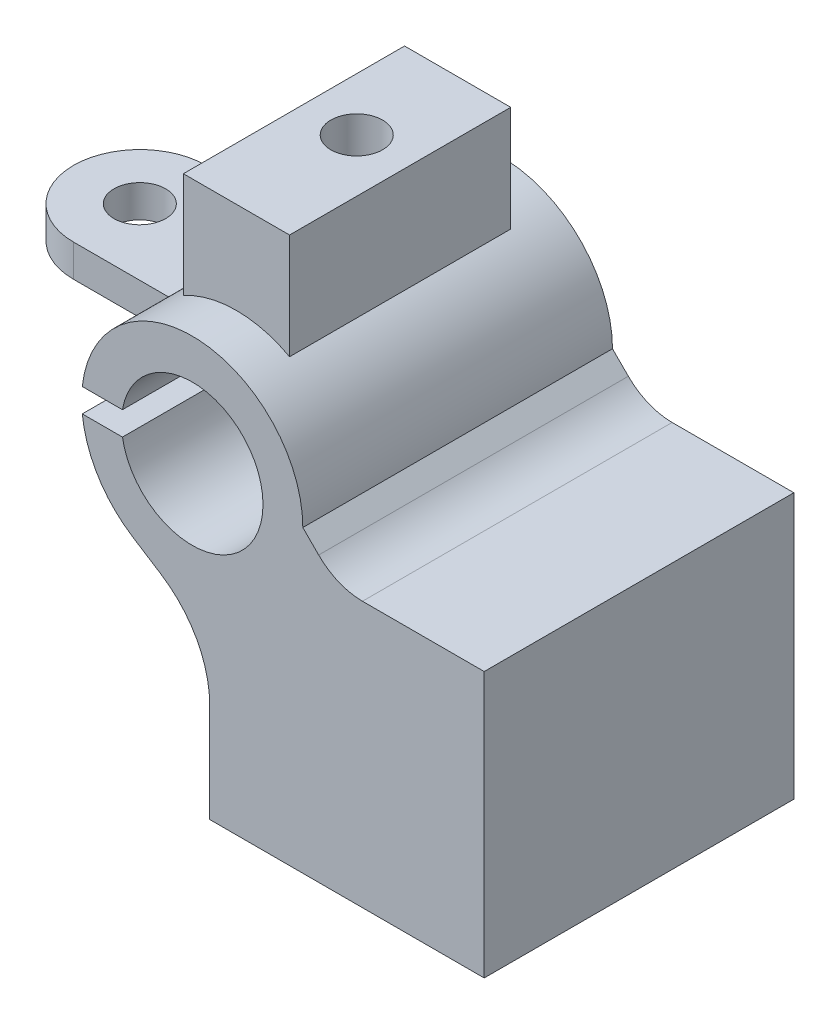
SolidWorks part; units mm, degrees
ref_plane "Front Plane" through (0, 0, 0) normal (0, 0, 1) x (1, 0, 0)
ref_plane "Top Plane" through (0, 0, 0) normal (0, 1, 0) x (1, 0, 0)
ref_plane "Right Plane" through (0, 0, 0) normal (1, 0, 0) x (0, 0, -1)
sketch "Sketch1" plane through (0, 0, 0) normal (0, 0, 1) x (1, 0, 0)
  line L0 (12.5, 0) -> (14.2931, -1.7931)
  line L1 (19.2428, -3.8433) -> (33, -3.8433)
  line L2 (33, -3.8433) -> (33, -33.8433)
  line L3 (33, -33.8433) -> (1.9777, -33.8433)
  line L4 (1.9777, -33.8433) -> (1.9777, -22.6745)
  line L6 (0, 0) -> (0, 50000) construction
  line L7 (-3.5519, -12.5684) -> (-6.74, -10.5272)
  line L8 (0, 0) -> (-50000, 0) construction
  line L9 (-7.8872, 1.3388) -> (-12.4281, 1.3388)
  line L10 (-7.8872, -1.3388) -> (-12.4281, -1.3388)
  line L11 (-6, 10.9659) -> (-6, 22.8852)
  line L12 (-6, 22.8852) -> (6, 22.8852)
  line L13 (6, 22.8852) -> (6, 10.9659)
  line L14 (-12.4281, 1.3388) -> (-30.9237, 1.3388)
  line L15 (-30.9237, 1.3388) -> (-30.9237, 4.9871)
  line L16 (-30.9237, 4.9871) -> (-11.4621, 4.9871)
  circle A0 centre (0, 0) radius 8
  arc A1 (12.5, 0) -> (-6.74, -10.5272) centre (0, 0) ccw
  arc A2 (14.2931, -1.7931) -> (19.2428, -3.8433) centre (19.2428, 3.1567) ccw
  arc A3 (1.9777, -22.6745) -> (-3.5519, -12.5684) centre (-10.0223, -22.6745) ccw
  point P24 (0, 0)
  point P30 (0, 0)
  point P31 (0, 0)
  point P32 (0, 0)
  point P33 (0, 0)
  dimension "D1" = 16
  dimension "D2" = 25
  dimension "D3" = 7
  dimension "D5" = 12
  dimension "D4" = 30
  dimension "D6" = 33
  dimension "D7" = 12
extrude "Boss-Extrude1" add sketch "Sketch1" along normal mid plane 35 contours A3 L4 L3 L2 L1 A2 L0 A1 L9 A0 L10 L7 region at (13.7485, -14.7845, 0)
extrude "Boss-Extrude2" add sketch "Sketch1<4>" along normal mid plane 15 separate body contours A1 L16 L15 L14 region at (-21.4817, 3.1784, 0)
sketch "Sketch1<4>" plane through (0, 0, 0) normal (0, 0, 1) x (1, 0, 0) same geometry as "Sketch1"
extrude "Boss-Extrude3" add sketch "Sketch1<5>" along normal mid plane 25 contours A1 L13 L12 L11 region at (0, 17.4341, 0)
sketch "Sketch1<5>" plane through (0, 0, 0) normal (0, 0, 1) x (1, 0, 0) same geometry as "Sketch1"
fillet "Fillet1" 2 edges at (-30.9237, 3.1629, 7.5) (-30.9237, 3.1629, -7.5) type full round first side face at (-21.469, 3.1721, 7.5) second side face at (-21.469, 3.1721, -7.5) middle face at (-30.9237, 3.1629, 0)
hole_wizard "#75 (0.23) Diameter Hole1" positions "Sketch7" profile "Sketch3" hole size "#75" standard "ANSI Inch"
sketch "Sketch7" plane through (0, 4.9871, 0) normal (0, 1, 0) x (1, 0, 0)
  point P0 (-23.4237, 0)
sketch "Sketch3" plane through (-23.4237, 4.9871, 0) normal (1, 0, 0) x (0, 0, 1)
  line L0 (0, 0) -> (0, 21.7551)
  line L1 (0, 21.7551) -> (2.921, 20)
  line L2 (2.921, 20) -> (2.921, 0)
  line L5 (2.921, 0) -> (0, 0)
  line L10 (0, 21.7551) -> (-2.921, 20) construction
  line L11 (0, -6.35) -> (0, 107.95) construction
  dimension "Hole Dia." = 5.842
  dimension "Hole Depth" = 20
  dimension "Drill Angle" = 118
hole_wizard "#97 (0.23) Diameter Hole1" positions "Sketch8" profile "Sketch9" hole size "#97" standard "ANSI Inch"
sketch "Sketch8" plane through (0, 22.8852, 0) normal (0, 1, 0) x (1, 0, 0)
  point P0 (0, 1.0922)
sketch "Sketch9" plane through (0, 22.8852, -1.0922) normal (1, 0, 0) x (0, 0, 1)
  line L0 (0, 0) -> (0, 11.7551)
  line L1 (0, 11.7551) -> (2.921, 10)
  line L2 (2.921, 10) -> (2.921, 0)
  line L5 (2.921, 0) -> (0, 0)
  line L10 (0, 11.7551) -> (-2.921, 10) construction
  line L11 (0, -6.35) -> (0, 107.95) construction
  dimension "Hole Dia." = 5.842
  dimension "Hole Depth" = 10
  dimension "Drill Angle" = 118
